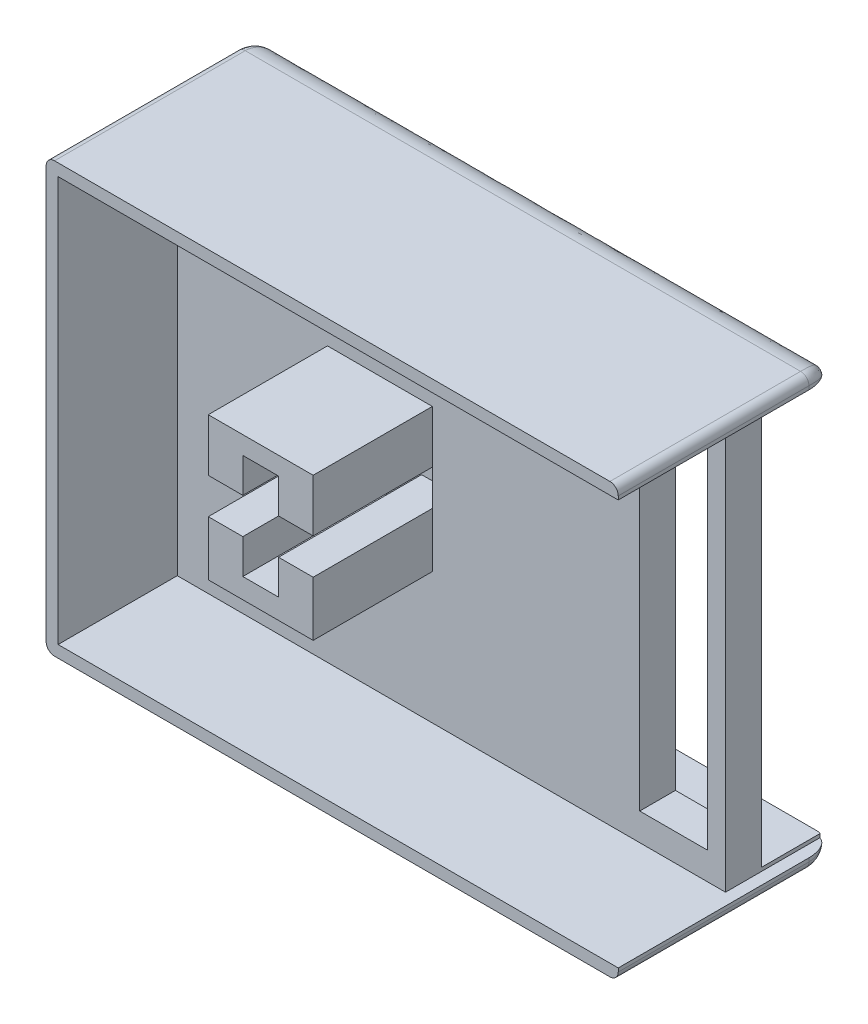
SolidWorks part; units mm, degrees
ref_plane "Front Plane" through (0, 0, 0) normal (0, 0, 1) x (1, 0, 0)
ref_plane "Top Plane" through (0, 0, 0) normal (0, 1, 0) x (1, 0, 0)
ref_plane "Right Plane" through (0, 0, 0) normal (1, 0, 0) x (0, 0, -1)
sketch "Sketch1" plane through (0, 0, 0) normal (0, 0, 1) x (1, 0, 0)
  line L1 (-12, -9) -> (12, -9)
  line L2 (-12, -9) -> (-12, 9)
  line L3 (-12, 9) -> (12, 9)
  line L4 (12, -9) -> (12, 9)
  line L5 (-12, -9) -> (12, 9) construction
  line L6 (-12, 9) -> (12, -9) construction
  point P0 (0, 0)
  dimension "D1" = 24
  dimension "D2" = 18
extrude "Boss-Extrude1" add sketch "Sketch1" along normal blind 13
fillet "Fillet1" radius 0.65 4 edges at (-12, 0, 0) (0, -9, 0) (12, 0, 0) (0, 9, 0) second distance 1 first distance on face at (0, 0, 0)
fillet "Fillet2" radius 0.35 8 edges
sketch "Sketch2" plane through (0, 0, 13) normal (0, 0, 1) x (1, 0, 0)
  line L0 (-11.65, -9) -> (11.65, -9) construction
  line L1 (11.5, 8.5) -> (-11.5, 8.5)
  line L2 (11.5, 8.5) -> (11.5, -8.5)
  line L3 (11.5, -8.5) -> (-11.5, -8.5)
  line L4 (-11.5, 8.5) -> (-11.5, -8.5)
  line L5 (12, -8.65) -> (12, 8.65) construction
  line L6 (11.65, 9) -> (-11.65, 9) construction
  line L7 (-12, 8.65) -> (-12, -8.65) construction
  dimension "D1" = 0.5
  dimension "D2" = 0.5
  dimension "D3" = 0.5
  dimension "D4" = 0.5
extrude "Cut-Extrude1" cut sketch "Sketch2" against normal blind 9
sketch "Sketch11" plane through (0, 0, 4) normal (0, 0, 1) x (1, 0, 0)
  line L1 (-5.2, -3) -> (-0.8, -3)
  line L2 (-5.2, -3) -> (-5.2, 3)
  line L3 (-5.2, 3) -> (-0.8, 3)
  line L4 (-0.8, -3) -> (-0.8, 3)
  line L5 (-5.2, -3) -> (-0.8, 3) construction
  line L6 (-5.2, 3) -> (-0.8, -3) construction
  line L7 (-11.5, 8.5) -> (-11.5, -8.5) construction
  point P0 (0, 0)
  dimension "D1" = 6
  dimension "D2" = 4.4
  dimension "D3" = 6.3
extrude "Boss-Extrude4" add sketch "Sketch11" along normal blind 9
sketch "Sketch12" plane through (0, 0, 13) normal (0, 0, 1) x (1, 0, 0)
  line L0 (-5.2, 3) -> (-5.2, -3) construction
  line L1 (-0.8, 0.7955) -> (-5.2, 0.7955)
  line L2 (-0.8, 0.7955) -> (-0.8, -0.7045)
  line L3 (-0.8, -0.7045) -> (-5.2, -0.7045)
  line L4 (-5.2, 0.7955) -> (-5.2, -0.7045)
  line L5 (-0.8, 0.7955) -> (-5.2, -0.7045) construction
  line L6 (-0.8, -0.7045) -> (-5.2, 0.7955) construction
  point P0 (-3, 0.0455)
  dimension "D1" = 1.5
extrude "Cut-Extrude6" cut sketch "Sketch12" against normal blind 10
sketch "Sketch13" plane through (0, 0, 13) normal (0, 0, 1) x (1, 0, 0)
  line L0 (-5.2, 0.7955) -> (-5.2, -0.7045) construction
  line L1 (-3.75, -2.1545) -> (-2.25, -2.1545)
  line L2 (-3.75, -2.1545) -> (-3.75, 2.2455)
  line L3 (-3.75, 2.2455) -> (-2.25, 2.2455)
  line L4 (-2.25, -2.1545) -> (-2.25, 2.2455)
  line L5 (-3.75, -2.1545) -> (-2.25, 2.2455) construction
  line L6 (-3.75, 2.2455) -> (-2.25, -2.1545) construction
  line L7 (-0.8, 0.7955) -> (-5.2, 0.7955) construction
  point P0 (-3, 0.0455)
extrude "Cut-Extrude7" cut sketch "Sketch13" against normal blind 10
sketch "Sketch14" plane through (0, 0, 13) normal (0, 0, 1) x (1, 0, 0)
  line L0 (12, -8.65) -> (12, 8.65) construction
  line L1 (11.5, 8.5) -> (12, 8.5)
  line L2 (11.5, 8.5) -> (11.5, -8.5)
  line L3 (11.5, -8.5) -> (12, -8.5)
  line L4 (12, 8.5) -> (12, -8.5)
extrude "Cut-Extrude8" cut sketch "Sketch14" against normal through all
sketch "Sketch17" plane through (0, 0, 0) normal (0, 0, -1) x (-1, 0, 0)
  line L0 (-11.35, -8.35) -> (11.35, -8.35) construction
  line L1 (-11.35, 8.35) -> (6.65, 8.35)
  line L2 (-11.35, 8.35) -> (-11.35, -8.35)
  line L3 (-11.35, -8.35) -> (6.65, -8.35)
  line L4 (6.65, 8.35) -> (6.65, -8.35)
  dimension "D1" = 18
extrude "Cut-Extrude9" cut sketch "Sketch17" against normal blind 2.5
sketch "Sketch18" plane through (11.35, 0, 0) normal (-1, 0, 0) x (0, 0, 1)
  line L0 (2.5, 8.35) -> (2.5, -8.35) construction
  line L1 (0, 8.35) -> (2.5, 8.35)
  line L2 (0, 8.35) -> (0, -8.35)
  line L3 (0, -8.35) -> (2.5, -8.35)
  line L4 (2.5, 8.35) -> (2.5, -8.35)
extrude "Cut-Extrude10" cut sketch "Sketch18" against normal through all
sketch "Sketch19" plane through (0, 0, 2.5) normal (0, 0, -1) x (-1, 0, 0)
  line L0 (6.65, 8.35) -> (-11.5, 8.35) construction
  line L1 (-10.75, -7.35) -> (-7.9, -7.35)
  line L2 (-10.75, -7.35) -> (-10.75, 7.35)
  line L3 (-10.75, 7.35) -> (-7.9, 7.35)
  line L4 (-7.9, -7.35) -> (-7.9, 7.35)
  line L5 (-10.75, -7.35) -> (-7.9, 7.35) construction
  line L6 (-10.75, 7.35) -> (-7.9, -7.35) construction
  line L7 (-11.5, -8.35) -> (6.65, -8.35) construction
  line L8 (-11.5, -8.35) -> (-11.5, 8.35) construction
  point P0 (-7.9369, 0)
  dimension "D1" = 1
  dimension "D2" = 1
  dimension "D3" = 2.85
  dimension "D4" = 0.75
extrude "Cut-Extrude11" cut sketch "Sketch19" against normal through all
sketch "Sketch20" plane through (0, 0, 13) normal (0, 0, 1) x (1, 0, 0)
  line L0 (11.65, 9) -> (-11.65, 9) construction
  line L1 (-12, 8.65) -> (-12, -8.65) construction
  line L2 (-12, 9) -> (12, 9)
  line L3 (-12, 9) -> (-12, -9)
  line L4 (-12, -9) -> (12, -9)
  line L5 (12, 9) -> (12, -9)
  line L6 (-11.65, -9) -> (11.65, -9) construction
  line L7 (12, -8.5) -> (12, 8.5) construction
extrude "Cut-Extrude12" cut sketch "Sketch20" against normal blind 4
